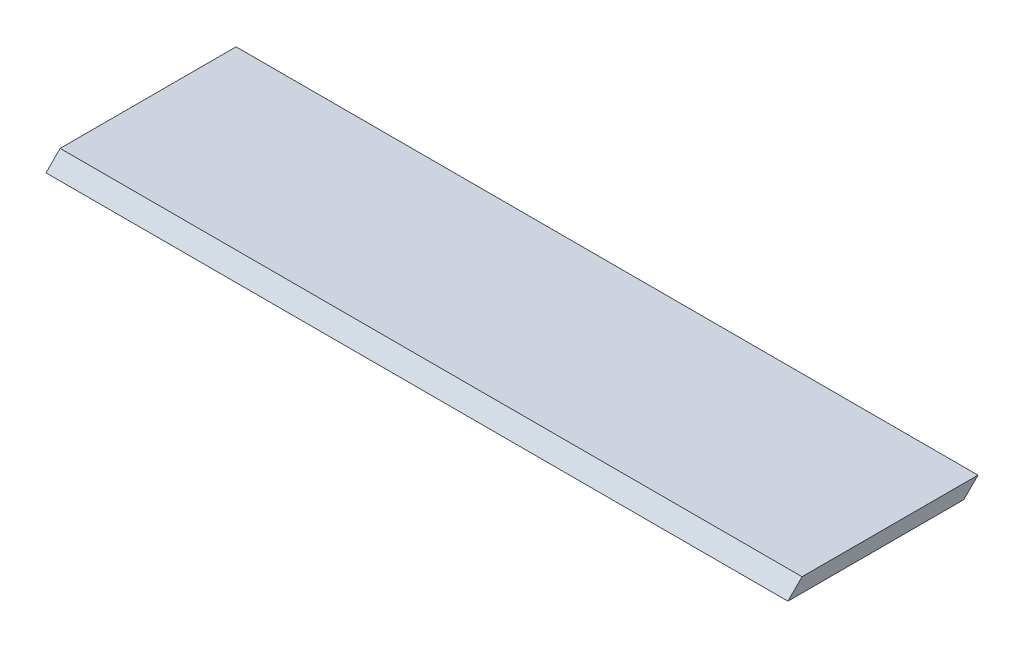
SolidWorks part; units mm, degrees
ref_plane "Front Plane" through (0, 0, 0) normal (0, 0, 1) x (1, 0, 0)
ref_plane "Top Plane" through (0, 0, 0) normal (0, 1, 0) x (1, 0, 0)
ref_plane "Right Plane" through (0, 0, 0) normal (1, 0, 0) x (0, 0, -1)
sketch "Sketch2" plane through (0, 0, 0) normal (0, 1, 0) x (1, 0, 0)
  line L2 (-52.5, 18.1181) -> (-52.5, -8.7819)
  line L12 (52.5, 18.1181) -> (52.5, -8.7819)
  line L17 (-52.5, 18.1181) -> (52.5, 18.1181)
  line L19 (-52.5, -8.7819) -> (52.5, -8.7819)
  point P0 (0, 0)
  dimension "D4" = 26.9
extrude "Boss-Extrude1" add sketch "Sketch2" along normal blind 2
chamfer "Chamfer1" distance 2 angle 45 1 edges at (0, 2, 8.7819)
chamfer "Chamfer2" distance 2 angle 45 1 edges at (0, 0, -18.1181)
